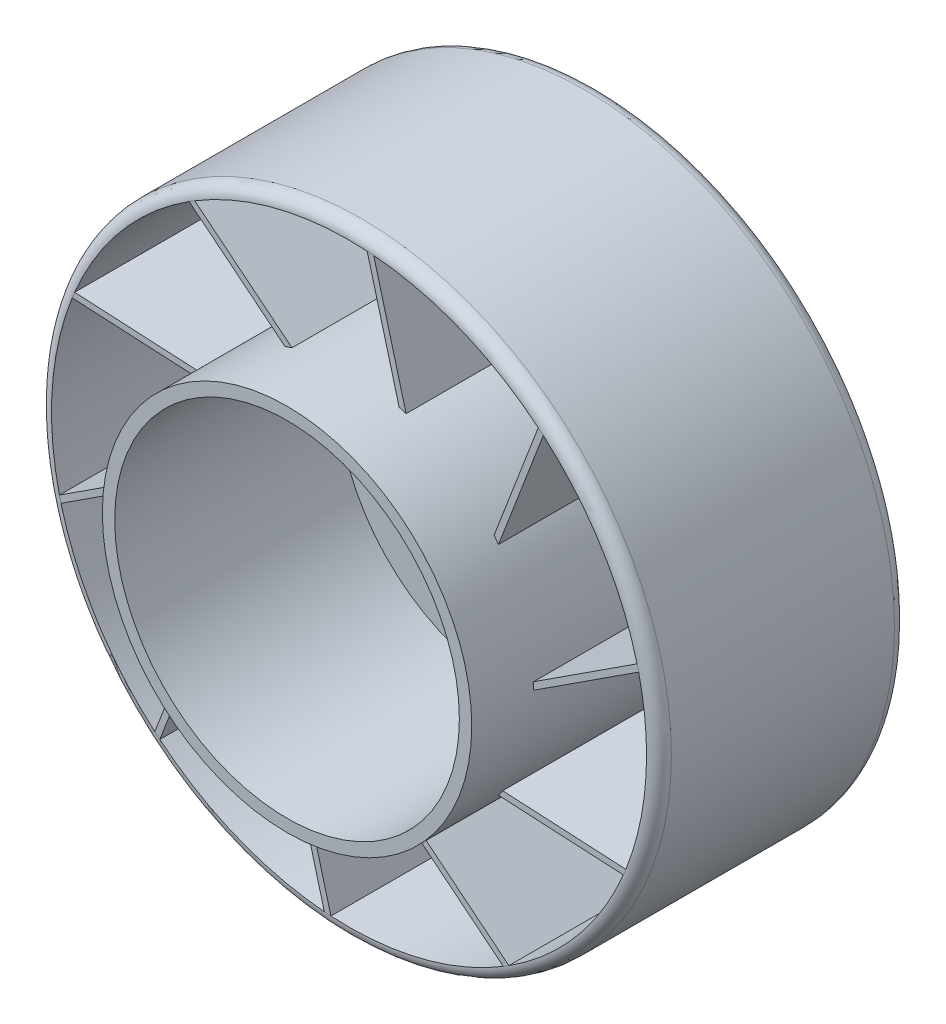
SolidWorks part; units mm, degrees
ref_plane "Front Plane" through (0, 0, 0) normal (0, 0, 1) x (1, 0, 0)
ref_plane "Top Plane" through (0, 0, 0) normal (0, 1, 0) x (1, 0, 0)
ref_plane "Right Plane" through (0, 0, 0) normal (1, 0, 0) x (0, 0, -1)
sketch "Sketch1" plane through (0, 0, 0) normal (0, 0, 1) x (1, 0, 0)
  line L0 (-33.9097, 0) -> (38.3352, 0) construction
  line L1 (0, 26.8691) -> (0, -27.214) construction
  line L2 (14.9, 0) -> (23.362, 5.4972)
  line L3 (14.8884, 0.5887) -> (23.2351, 6.011)
  line L4 (12.391, -8.2749) -> (22.3307, -8.7943)
  line L5 (12.0544, -8.758) -> (22.1314, -9.2845)
  line L6 (5.1606, -13.9778) -> (12.8968, -20.2404)
  line L7 (4.6044, -14.1707) -> (12.4474, -20.5198)
  line L8 (-4.0409, -14.3416) -> (-1.4633, -23.9554)
  line L9 (-4.6044, -14.1707) -> (-1.9911, -23.9173)
  line L10 (-11.6989, -9.2274) -> (-15.2644, -18.5202)
  line L11 (-12.0544, -8.758) -> (-15.6691, -18.1791)
  line L12 (-14.8884, -0.5887) -> (-23.2351, -6.011)
  line L13 (-14.9, 0) -> (-23.362, -5.4972)
  line L14 (-12.391, 8.2749) -> (-22.3307, 8.7943)
  line L15 (-12.0544, 8.758) -> (-22.1314, 9.2845)
  line L16 (-5.1606, 13.9778) -> (-12.8968, 20.2404)
  line L17 (-4.6044, 14.1707) -> (-12.4474, 20.5198)
  line L18 (4.0409, 14.3416) -> (1.4633, 23.9554)
  line L19 (4.6044, 14.1707) -> (1.9911, 23.9173)
  line L20 (11.6989, 9.2274) -> (15.2644, 18.5202)
  line L21 (12.0544, 8.758) -> (15.6691, 18.1791)
  circle A0 centre (0, 0) radius 13.9
  arc A1 (14.8884, 0.5887) -> (12.0544, 8.758) centre (0, 0) ccw
  circle A2 centre (0, 0) radius 25
  arc A3 (23.2351, 6.011) -> (15.6691, 18.1791) centre (0, 0) ccw
  circle A4 centre (0, 0) radius 24 construction
  arc A5 (11.6989, 9.2274) -> (4.6044, 14.1707) centre (0, 0) ccw
  arc A6 (15.2644, 18.5202) -> (1.9911, 23.9173) centre (0, 0) ccw
  arc A7 (1.4633, 23.9554) -> (-12.4474, 20.5198) centre (0, 0) ccw
  arc A8 (4.0409, 14.3416) -> (-4.6044, 14.1707) centre (0, 0) ccw
  arc A9 (-5.1606, 13.9778) -> (-12.0544, 8.758) centre (0, 0) ccw
  arc A10 (-12.8968, 20.2404) -> (-22.1314, 9.2845) centre (0, 0) ccw
  arc A11 (-22.3307, 8.7943) -> (-23.362, -5.4972) centre (0, 0) ccw
  arc A12 (-12.391, 8.2749) -> (-14.9, 0) centre (0, 0) ccw
  arc A13 (-14.8884, -0.5887) -> (-12.0544, -8.758) centre (0, 0) ccw
  arc A14 (-23.2351, -6.011) -> (-15.6691, -18.1791) centre (0, 0) ccw
  arc A15 (-11.6989, -9.2274) -> (-4.6044, -14.1707) centre (0, 0) ccw
  arc A16 (-15.2644, -18.5202) -> (-1.9911, -23.9173) centre (0, 0) ccw
  arc A17 (-4.0409, -14.3416) -> (4.6044, -14.1707) centre (0, 0) ccw
  arc A18 (5.1606, -13.9778) -> (12.0544, -8.758) centre (0, 0) ccw
  arc A19 (12.391, -8.2749) -> (14.9, 0) centre (0, 0) ccw
  arc A20 (12.8968, -20.2404) -> (22.1314, -9.2845) centre (0, 0) ccw
  arc A21 (-1.4633, -23.9554) -> (12.4474, -20.5198) centre (0, 0) ccw
  arc A22 (22.3307, -8.7943) -> (23.362, 5.4972) centre (0, 0) ccw
  dimension "D1" = 27.8
  dimension "D2" = 1
  dimension "D3" = 50
  dimension "D6" = 0.5
  dimension "D4" = 1
  dimension "D5" = 10
extrude "Boss-Extrude1" add sketch "Sketch1" along normal blind 20
fillet "Fillet1" radius 1 2 edges at (25, 0, 0) (25, 0, 20)
sketch "Sketch2" plane through (0, 0, 0) normal (0, 0, -1) x (-1, 0, 0)
  circle A0 centre (0, 0) radius 13.9 construction
  circle A1 centre (0, 0) radius 13.9
extrude "Boss-Extrude2" add sketch "Sketch2" against normal blind 7
sketch "Sketch3" plane through (0, 0, 0) normal (0, 0, -1) x (-1, 0, 0)
  circle A0 centre (0, 0) radius 4.125
  dimension "D1" = 8.25
extrude "Cut-Extrude1" cut sketch "Sketch3" against normal through all
sketch "Sketch4" plane through (0, 0, 7) normal (0, 0, 1) x (1, 0, 0)
  circle A0 centre (0, 0) radius 4.6
  dimension "D1" = 9.2
extrude "Cut-Extrude2" cut sketch "Sketch4" against normal blind 2.3
sketch "Sketch8" plane through (0, 0, 20) normal (0, 0, 1) x (1, 0, 0)
  circle A2 centre (0, 0) radius 13.9 construction
  circle A3 centre (0, 0) radius 14.9
  circle A4 centre (0, 0) radius 14.9
  circle A5 centre (0, 0) radius 13.9
  dimension "D1" = 1
extrude "Boss-Extrude3" add sketch "Sketch8" along normal blind 5
